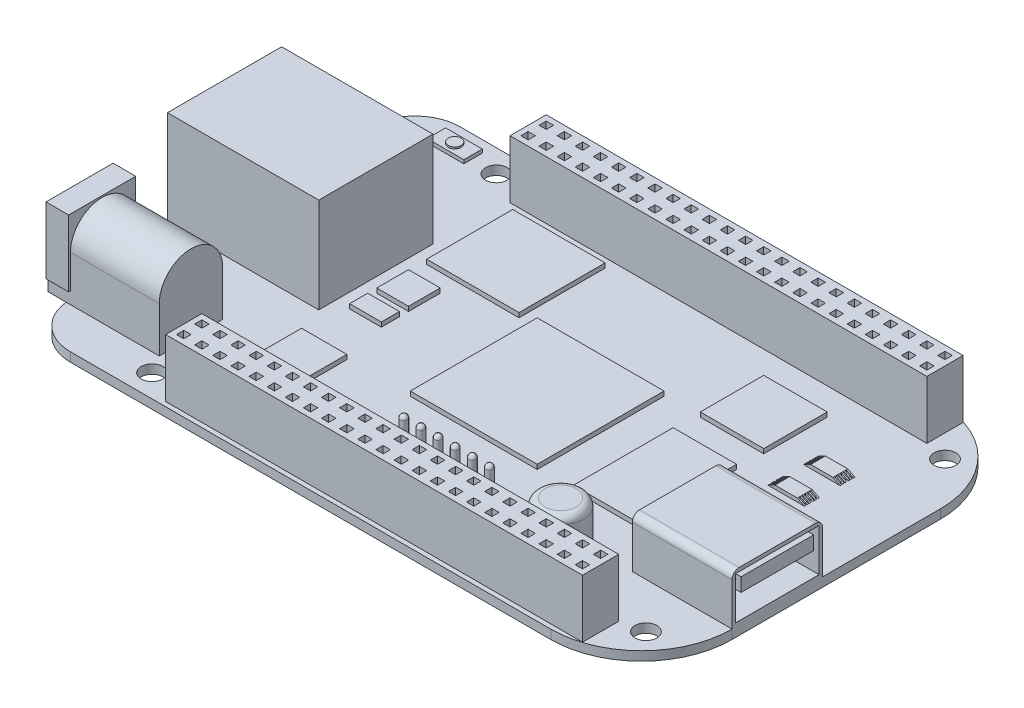
SolidWorks part; units mm, degrees
material "ABS"
ref_plane "Front Plane" through (0, 0, 0) normal (0, 0, 1) x (1, 0, 0)
ref_plane "Top Plane" through (0, 0, 0) normal (0, 1, 0) x (1, 0, 0)
ref_plane "Right Plane" through (0, 0, 0) normal (1, 0, 0) x (0, 0, -1)
sketch "Sketch1" plane through (0, 0, 0) normal (0, 1, 0) x (1, 0, 0)
  line L1 (-12.7, 0) -> (-80.01, 0)
  line L2 (0, 12.7) -> (0, 41.91)
  line L3 (-12.7, 54.61) -> (-80.01, 54.61)
  line L4 (-86.36, 6.35) -> (-86.36, 48.26)
  arc A0 (0, 12.7) -> (-12.7, 0) centre (-12.7, 12.7) cw
  arc A1 (0, 41.91) -> (-12.7, 54.61) centre (-12.7, 41.91) ccw
  arc A2 (-86.36, 6.35) -> (-80.01, 0) centre (-80.01, 6.35) ccw
  arc A3 (-86.36, 48.26) -> (-80.01, 54.61) centre (-80.01, 48.26) cw
  point P7 (0, 0)
  point P10 (0, 54.61)
  point P13 (-86.36, 0)
  dimension "D3" = 12.7
  dimension "D4" = 6.35
  dimension "D1" = 86.36
  dimension "D2" = 54.61
extrude "Boss-Extrude1" add sketch "Sketch1" along normal blind 1.27
sketch "Sketch2" plane through (0, 1.27, 0) normal (0, 1, 0) x (1, 0, 0)
  line L0 (-80.01, 0) -> (-12.7, 0) construction
  line L2 (-71.755, 51.435) -> (-71.755, 3.175) construction
  line L3 (-86.36, 48.26) -> (-86.36, 6.35) construction
  line L4 (-5.715, 48.26) -> (-5.715, 6.35) construction
  circle A0 centre (-71.755, 51.435) radius 1.524
  circle A1 centre (-71.755, 3.175) radius 1.524
  circle A2 centre (-5.715, 48.26) radius 1.524
  circle A3 centre (-5.715, 6.35) radius 1.524
  dimension "D7" = 3.048
  dimension "D1" = 48.26
  dimension "D2" = 41.91
  dimension "D3" = 6.35
  dimension "D4" = 14.605
  dimension "D5" = 80.645
  dimension "D6" = 3.175
extrude "Cut-Extrude1" cut sketch "Sketch2" along direction (0, -1, 0) on the side against the normal up to surface (1.27 mm away) up to face at (-44.4387, 0, -27.305)
sketch "Sketch3" plane through (0, 1.27, 0) normal (0, 1, 0) x (1, 0, 0)
  line L0 (-10.16, 48.895) -> (-10.16, 50.165) construction
  line L1 (-67.31, 53.975) -> (-8.89, 53.975)
  line L2 (-67.31, 53.975) -> (-67.31, 48.895)
  line L3 (-67.31, 48.895) -> (-8.89, 48.895)
  line L4 (-8.89, 53.975) -> (-8.89, 48.895)
  line L5 (-86.36, 27.305) -> (0, 27.305) construction
  line L6 (0, 12.7) -> (0, 41.91) construction
  line L7 (-66.548, 4.953) -> (-66.548, 3.937)
  line L8 (-66.548, 4.953) -> (-65.532, 4.953)
  line L9 (-10.16, 50.165) -> (-10.16, 52.705) construction
  line L10 (-10.16, 52.705) -> (-10.16, 53.975) construction
  line L11 (-13.208, 52.197) -> (-12.192, 52.197)
  line L12 (-10.668, 53.213) -> (-9.652, 53.213)
  line L13 (-10.668, 53.213) -> (-10.668, 52.197)
  line L14 (-10.668, 52.197) -> (-9.652, 52.197)
  line L15 (-9.652, 53.213) -> (-9.652, 52.197)
  line L16 (-10.668, 53.213) -> (-9.652, 52.197) construction
  line L17 (-10.668, 52.197) -> (-9.652, 53.213) construction
  line L18 (-10.668, 49.657) -> (-9.652, 49.657)
  line L19 (-10.668, 49.657) -> (-10.668, 50.673)
  line L20 (-10.668, 50.673) -> (-9.652, 50.673)
  line L21 (-9.652, 49.657) -> (-9.652, 50.673)
  line L22 (-10.668, 49.657) -> (-9.652, 50.673) construction
  line L23 (-10.668, 50.673) -> (-9.652, 49.657) construction
  line L24 (-13.208, 53.213) -> (-13.208, 52.197)
  line L25 (-13.208, 53.213) -> (-12.192, 53.213)
  line L26 (-12.192, 53.213) -> (-12.192, 52.197)
  line L27 (-13.208, 50.673) -> (-12.192, 50.673)
  line L28 (-12.192, 49.657) -> (-12.192, 50.673)
  line L29 (-13.208, 49.657) -> (-12.192, 49.657)
  line L30 (-13.208, 49.657) -> (-13.208, 50.673)
  line L31 (-15.748, 52.197) -> (-14.732, 52.197)
  line L32 (-15.748, 53.213) -> (-15.748, 52.197)
  line L33 (-15.748, 53.213) -> (-14.732, 53.213)
  line L34 (-14.732, 53.213) -> (-14.732, 52.197)
  line L35 (-15.748, 50.673) -> (-14.732, 50.673)
  line L36 (-14.732, 49.657) -> (-14.732, 50.673)
  line L37 (-15.748, 49.657) -> (-14.732, 49.657)
  line L38 (-15.748, 49.657) -> (-15.748, 50.673)
  line L39 (-18.288, 52.197) -> (-17.272, 52.197)
  line L40 (-18.288, 53.213) -> (-18.288, 52.197)
  line L41 (-18.288, 53.213) -> (-17.272, 53.213)
  line L42 (-17.272, 53.213) -> (-17.272, 52.197)
  line L43 (-18.288, 50.673) -> (-17.272, 50.673)
  line L44 (-17.272, 49.657) -> (-17.272, 50.673)
  line L45 (-18.288, 49.657) -> (-17.272, 49.657)
  line L46 (-18.288, 49.657) -> (-18.288, 50.673)
  line L47 (-20.828, 52.197) -> (-19.812, 52.197)
  line L48 (-20.828, 53.213) -> (-20.828, 52.197)
  line L49 (-20.828, 53.213) -> (-19.812, 53.213)
  line L50 (-19.812, 53.213) -> (-19.812, 52.197)
  line L51 (-20.828, 50.673) -> (-19.812, 50.673)
  line L52 (-19.812, 49.657) -> (-19.812, 50.673)
  line L53 (-20.828, 49.657) -> (-19.812, 49.657)
  line L54 (-20.828, 49.657) -> (-20.828, 50.673)
  line L55 (-23.368, 52.197) -> (-22.352, 52.197)
  line L56 (-23.368, 53.213) -> (-23.368, 52.197)
  line L57 (-23.368, 53.213) -> (-22.352, 53.213)
  line L58 (-22.352, 53.213) -> (-22.352, 52.197)
  line L59 (-23.368, 50.673) -> (-22.352, 50.673)
  line L60 (-22.352, 49.657) -> (-22.352, 50.673)
  line L61 (-23.368, 49.657) -> (-22.352, 49.657)
  line L62 (-23.368, 49.657) -> (-23.368, 50.673)
  line L63 (-25.908, 52.197) -> (-24.892, 52.197)
  line L64 (-25.908, 53.213) -> (-25.908, 52.197)
  line L65 (-25.908, 53.213) -> (-24.892, 53.213)
  line L66 (-24.892, 53.213) -> (-24.892, 52.197)
  line L67 (-25.908, 50.673) -> (-24.892, 50.673)
  line L68 (-24.892, 49.657) -> (-24.892, 50.673)
  line L69 (-25.908, 49.657) -> (-24.892, 49.657)
  line L70 (-25.908, 49.657) -> (-25.908, 50.673)
  line L71 (-28.448, 52.197) -> (-27.432, 52.197)
  line L72 (-28.448, 53.213) -> (-28.448, 52.197)
  line L73 (-28.448, 53.213) -> (-27.432, 53.213)
  line L74 (-27.432, 53.213) -> (-27.432, 52.197)
  line L75 (-28.448, 50.673) -> (-27.432, 50.673)
  line L76 (-27.432, 49.657) -> (-27.432, 50.673)
  line L77 (-28.448, 49.657) -> (-27.432, 49.657)
  line L78 (-28.448, 49.657) -> (-28.448, 50.673)
  line L79 (-30.988, 52.197) -> (-29.972, 52.197)
  line L80 (-30.988, 53.213) -> (-30.988, 52.197)
  line L81 (-30.988, 53.213) -> (-29.972, 53.213)
  line L82 (-29.972, 53.213) -> (-29.972, 52.197)
  line L83 (-30.988, 50.673) -> (-29.972, 50.673)
  line L84 (-29.972, 49.657) -> (-29.972, 50.673)
  line L85 (-30.988, 49.657) -> (-29.972, 49.657)
  line L86 (-30.988, 49.657) -> (-30.988, 50.673)
  line L87 (-33.528, 52.197) -> (-32.512, 52.197)
  line L88 (-33.528, 53.213) -> (-33.528, 52.197)
  line L89 (-33.528, 53.213) -> (-32.512, 53.213)
  line L90 (-32.512, 53.213) -> (-32.512, 52.197)
  line L91 (-33.528, 50.673) -> (-32.512, 50.673)
  line L92 (-32.512, 49.657) -> (-32.512, 50.673)
  line L93 (-33.528, 49.657) -> (-32.512, 49.657)
  line L94 (-33.528, 49.657) -> (-33.528, 50.673)
  line L95 (-36.068, 52.197) -> (-35.052, 52.197)
  line L96 (-36.068, 53.213) -> (-36.068, 52.197)
  line L97 (-36.068, 53.213) -> (-35.052, 53.213)
  line L98 (-35.052, 53.213) -> (-35.052, 52.197)
  line L99 (-36.068, 50.673) -> (-35.052, 50.673)
  line L100 (-35.052, 49.657) -> (-35.052, 50.673)
  line L101 (-36.068, 49.657) -> (-35.052, 49.657)
  line L102 (-36.068, 49.657) -> (-36.068, 50.673)
  line L103 (-38.608, 52.197) -> (-37.592, 52.197)
  line L104 (-38.608, 53.213) -> (-38.608, 52.197)
  line L105 (-38.608, 53.213) -> (-37.592, 53.213)
  line L106 (-37.592, 53.213) -> (-37.592, 52.197)
  line L107 (-38.608, 50.673) -> (-37.592, 50.673)
  line L108 (-37.592, 49.657) -> (-37.592, 50.673)
  line L109 (-38.608, 49.657) -> (-37.592, 49.657)
  line L110 (-38.608, 49.657) -> (-38.608, 50.673)
  line L111 (-41.148, 52.197) -> (-40.132, 52.197)
  line L112 (-41.148, 53.213) -> (-41.148, 52.197)
  line L113 (-41.148, 53.213) -> (-40.132, 53.213)
  line L114 (-40.132, 53.213) -> (-40.132, 52.197)
  line L115 (-41.148, 50.673) -> (-40.132, 50.673)
  line L116 (-40.132, 49.657) -> (-40.132, 50.673)
  line L117 (-41.148, 49.657) -> (-40.132, 49.657)
  line L118 (-41.148, 49.657) -> (-41.148, 50.673)
  line L119 (-43.688, 52.197) -> (-42.672, 52.197)
  line L120 (-43.688, 53.213) -> (-43.688, 52.197)
  line L121 (-43.688, 53.213) -> (-42.672, 53.213)
  line L122 (-42.672, 53.213) -> (-42.672, 52.197)
  line L123 (-43.688, 50.673) -> (-42.672, 50.673)
  line L124 (-42.672, 49.657) -> (-42.672, 50.673)
  line L125 (-43.688, 49.657) -> (-42.672, 49.657)
  line L126 (-43.688, 49.657) -> (-43.688, 50.673)
  line L127 (-46.228, 52.197) -> (-45.212, 52.197)
  line L128 (-46.228, 53.213) -> (-46.228, 52.197)
  line L129 (-46.228, 53.213) -> (-45.212, 53.213)
  line L130 (-45.212, 53.213) -> (-45.212, 52.197)
  line L131 (-46.228, 50.673) -> (-45.212, 50.673)
  line L132 (-45.212, 49.657) -> (-45.212, 50.673)
  line L133 (-46.228, 49.657) -> (-45.212, 49.657)
  line L134 (-46.228, 49.657) -> (-46.228, 50.673)
  line L135 (-48.768, 52.197) -> (-47.752, 52.197)
  line L136 (-48.768, 53.213) -> (-48.768, 52.197)
  line L137 (-48.768, 53.213) -> (-47.752, 53.213)
  line L138 (-47.752, 53.213) -> (-47.752, 52.197)
  line L139 (-48.768, 50.673) -> (-47.752, 50.673)
  line L140 (-47.752, 49.657) -> (-47.752, 50.673)
  line L141 (-48.768, 49.657) -> (-47.752, 49.657)
  line L142 (-48.768, 49.657) -> (-48.768, 50.673)
  line L143 (-51.308, 52.197) -> (-50.292, 52.197)
  line L144 (-51.308, 53.213) -> (-51.308, 52.197)
  line L145 (-51.308, 53.213) -> (-50.292, 53.213)
  line L146 (-50.292, 53.213) -> (-50.292, 52.197)
  line L147 (-51.308, 50.673) -> (-50.292, 50.673)
  line L148 (-50.292, 49.657) -> (-50.292, 50.673)
  line L149 (-51.308, 49.657) -> (-50.292, 49.657)
  line L150 (-51.308, 49.657) -> (-51.308, 50.673)
  line L151 (-53.848, 52.197) -> (-52.832, 52.197)
  line L152 (-53.848, 53.213) -> (-53.848, 52.197)
  line L153 (-53.848, 53.213) -> (-52.832, 53.213)
  line L154 (-52.832, 53.213) -> (-52.832, 52.197)
  line L155 (-53.848, 50.673) -> (-52.832, 50.673)
  line L156 (-52.832, 49.657) -> (-52.832, 50.673)
  line L157 (-53.848, 49.657) -> (-52.832, 49.657)
  line L158 (-53.848, 49.657) -> (-53.848, 50.673)
  line L159 (-56.388, 52.197) -> (-55.372, 52.197)
  line L160 (-56.388, 53.213) -> (-56.388, 52.197)
  line L161 (-56.388, 53.213) -> (-55.372, 53.213)
  line L162 (-55.372, 53.213) -> (-55.372, 52.197)
  line L163 (-56.388, 50.673) -> (-55.372, 50.673)
  line L164 (-55.372, 49.657) -> (-55.372, 50.673)
  line L165 (-56.388, 49.657) -> (-55.372, 49.657)
  line L166 (-56.388, 49.657) -> (-56.388, 50.673)
  line L167 (-58.928, 52.197) -> (-57.912, 52.197)
  line L168 (-58.928, 53.213) -> (-58.928, 52.197)
  line L169 (-58.928, 53.213) -> (-57.912, 53.213)
  line L170 (-57.912, 53.213) -> (-57.912, 52.197)
  line L171 (-58.928, 50.673) -> (-57.912, 50.673)
  line L172 (-57.912, 49.657) -> (-57.912, 50.673)
  line L173 (-58.928, 49.657) -> (-57.912, 49.657)
  line L174 (-58.928, 49.657) -> (-58.928, 50.673)
  line L175 (-61.468, 52.197) -> (-60.452, 52.197)
  line L176 (-61.468, 53.213) -> (-61.468, 52.197)
  line L177 (-61.468, 53.213) -> (-60.452, 53.213)
  line L178 (-60.452, 53.213) -> (-60.452, 52.197)
  line L179 (-61.468, 50.673) -> (-60.452, 50.673)
  line L180 (-60.452, 49.657) -> (-60.452, 50.673)
  line L181 (-61.468, 49.657) -> (-60.452, 49.657)
  line L182 (-61.468, 49.657) -> (-61.468, 50.673)
  line L183 (-64.008, 52.197) -> (-62.992, 52.197)
  line L184 (-64.008, 53.213) -> (-64.008, 52.197)
  line L185 (-64.008, 53.213) -> (-62.992, 53.213)
  line L186 (-62.992, 53.213) -> (-62.992, 52.197)
  line L187 (-64.008, 50.673) -> (-62.992, 50.673)
  line L188 (-62.992, 49.657) -> (-62.992, 50.673)
  line L189 (-64.008, 49.657) -> (-62.992, 49.657)
  line L190 (-64.008, 49.657) -> (-64.008, 50.673)
  line L191 (-66.548, 52.197) -> (-65.532, 52.197)
  line L192 (-66.548, 53.213) -> (-66.548, 52.197)
  line L193 (-66.548, 53.213) -> (-65.532, 53.213)
  line L194 (-65.532, 53.213) -> (-65.532, 52.197)
  line L195 (-66.548, 50.673) -> (-65.532, 50.673)
  line L196 (-65.532, 49.657) -> (-65.532, 50.673)
  line L197 (-66.548, 49.657) -> (-65.532, 49.657)
  line L198 (-66.548, 49.657) -> (-66.548, 50.673)
  line L199 (-66.548, 49.657) -> (-65.532, 50.673) construction
  line L200 (-86.36, 48.26) -> (-86.36, 6.35) construction
  line L201 (-65.532, 4.953) -> (-65.532, 3.937)
  line L202 (-12.7, 54.61) -> (-80.01, 54.61) construction
  line L203 (-66.548, 3.937) -> (-65.532, 3.937)
  line L204 (-65.532, 1.397) -> (-65.532, 2.413)
  line L205 (-66.548, 1.397) -> (-65.532, 1.397)
  line L206 (-66.548, 1.397) -> (-66.548, 2.413)
  line L207 (-66.548, 2.413) -> (-65.532, 2.413)
  line L208 (-64.008, 4.953) -> (-64.008, 3.937)
  line L209 (-64.008, 4.953) -> (-62.992, 4.953)
  line L210 (-62.992, 4.953) -> (-62.992, 3.937)
  line L211 (-64.008, 3.937) -> (-62.992, 3.937)
  line L212 (-62.992, 1.397) -> (-62.992, 2.413)
  line L213 (-64.008, 1.397) -> (-62.992, 1.397)
  line L214 (-64.008, 1.397) -> (-64.008, 2.413)
  line L215 (-64.008, 2.413) -> (-62.992, 2.413)
  line L216 (-61.468, 4.953) -> (-61.468, 3.937)
  line L217 (-61.468, 4.953) -> (-60.452, 4.953)
  line L218 (-60.452, 4.953) -> (-60.452, 3.937)
  line L219 (-61.468, 3.937) -> (-60.452, 3.937)
  line L220 (-60.452, 1.397) -> (-60.452, 2.413)
  line L221 (-61.468, 1.397) -> (-60.452, 1.397)
  line L222 (-61.468, 1.397) -> (-61.468, 2.413)
  line L223 (-61.468, 2.413) -> (-60.452, 2.413)
  line L224 (-58.928, 4.953) -> (-58.928, 3.937)
  line L225 (-58.928, 4.953) -> (-57.912, 4.953)
  line L226 (-57.912, 4.953) -> (-57.912, 3.937)
  line L227 (-58.928, 3.937) -> (-57.912, 3.937)
  line L228 (-57.912, 1.397) -> (-57.912, 2.413)
  line L229 (-58.928, 1.397) -> (-57.912, 1.397)
  line L230 (-58.928, 1.397) -> (-58.928, 2.413)
  line L231 (-58.928, 2.413) -> (-57.912, 2.413)
  line L232 (-56.388, 4.953) -> (-56.388, 3.937)
  line L233 (-56.388, 4.953) -> (-55.372, 4.953)
  line L234 (-55.372, 4.953) -> (-55.372, 3.937)
  line L235 (-56.388, 3.937) -> (-55.372, 3.937)
  line L236 (-55.372, 1.397) -> (-55.372, 2.413)
  line L237 (-56.388, 1.397) -> (-55.372, 1.397)
  line L238 (-56.388, 1.397) -> (-56.388, 2.413)
  line L239 (-56.388, 2.413) -> (-55.372, 2.413)
  line L240 (-53.848, 4.953) -> (-53.848, 3.937)
  line L241 (-53.848, 4.953) -> (-52.832, 4.953)
  line L242 (-52.832, 4.953) -> (-52.832, 3.937)
  line L243 (-53.848, 3.937) -> (-52.832, 3.937)
  line L244 (-52.832, 1.397) -> (-52.832, 2.413)
  line L245 (-53.848, 1.397) -> (-52.832, 1.397)
  line L246 (-53.848, 1.397) -> (-53.848, 2.413)
  line L247 (-53.848, 2.413) -> (-52.832, 2.413)
  line L248 (-51.308, 4.953) -> (-51.308, 3.937)
  line L249 (-51.308, 4.953) -> (-50.292, 4.953)
  line L250 (-50.292, 4.953) -> (-50.292, 3.937)
  line L251 (-51.308, 3.937) -> (-50.292, 3.937)
  line L252 (-50.292, 1.397) -> (-50.292, 2.413)
  line L253 (-51.308, 1.397) -> (-50.292, 1.397)
  line L254 (-51.308, 1.397) -> (-51.308, 2.413)
  line L255 (-51.308, 2.413) -> (-50.292, 2.413)
  line L256 (-48.768, 4.953) -> (-48.768, 3.937)
  line L257 (-48.768, 4.953) -> (-47.752, 4.953)
  line L258 (-47.752, 4.953) -> (-47.752, 3.937)
  line L259 (-48.768, 3.937) -> (-47.752, 3.937)
  line L260 (-47.752, 1.397) -> (-47.752, 2.413)
  line L261 (-48.768, 1.397) -> (-47.752, 1.397)
  line L262 (-48.768, 1.397) -> (-48.768, 2.413)
  line L263 (-48.768, 2.413) -> (-47.752, 2.413)
  line L264 (-46.228, 4.953) -> (-46.228, 3.937)
  line L265 (-46.228, 4.953) -> (-45.212, 4.953)
  line L266 (-45.212, 4.953) -> (-45.212, 3.937)
  line L267 (-46.228, 3.937) -> (-45.212, 3.937)
  line L268 (-45.212, 1.397) -> (-45.212, 2.413)
  line L269 (-46.228, 1.397) -> (-45.212, 1.397)
  line L270 (-46.228, 1.397) -> (-46.228, 2.413)
  line L271 (-46.228, 2.413) -> (-45.212, 2.413)
  line L272 (-43.688, 4.953) -> (-43.688, 3.937)
  line L273 (-43.688, 4.953) -> (-42.672, 4.953)
  line L274 (-42.672, 4.953) -> (-42.672, 3.937)
  line L275 (-43.688, 3.937) -> (-42.672, 3.937)
  line L276 (-42.672, 1.397) -> (-42.672, 2.413)
  line L277 (-43.688, 1.397) -> (-42.672, 1.397)
  line L278 (-43.688, 1.397) -> (-43.688, 2.413)
  line L279 (-43.688, 2.413) -> (-42.672, 2.413)
  line L280 (-41.148, 4.953) -> (-41.148, 3.937)
  line L281 (-41.148, 4.953) -> (-40.132, 4.953)
  line L282 (-40.132, 4.953) -> (-40.132, 3.937)
  line L283 (-41.148, 3.937) -> (-40.132, 3.937)
  line L284 (-40.132, 1.397) -> (-40.132, 2.413)
  line L285 (-41.148, 1.397) -> (-40.132, 1.397)
  line L286 (-41.148, 1.397) -> (-41.148, 2.413)
  line L287 (-41.148, 2.413) -> (-40.132, 2.413)
  line L288 (-38.608, 4.953) -> (-38.608, 3.937)
  line L289 (-38.608, 4.953) -> (-37.592, 4.953)
  line L290 (-37.592, 4.953) -> (-37.592, 3.937)
  line L291 (-38.608, 3.937) -> (-37.592, 3.937)
  line L292 (-37.592, 1.397) -> (-37.592, 2.413)
  line L293 (-38.608, 1.397) -> (-37.592, 1.397)
  line L294 (-38.608, 1.397) -> (-38.608, 2.413)
  line L295 (-38.608, 2.413) -> (-37.592, 2.413)
  line L296 (-36.068, 4.953) -> (-36.068, 3.937)
  line L297 (-36.068, 4.953) -> (-35.052, 4.953)
  line L298 (-35.052, 4.953) -> (-35.052, 3.937)
  line L299 (-36.068, 3.937) -> (-35.052, 3.937)
  line L300 (-35.052, 1.397) -> (-35.052, 2.413)
  line L301 (-36.068, 1.397) -> (-35.052, 1.397)
  line L302 (-36.068, 1.397) -> (-36.068, 2.413)
  line L303 (-36.068, 2.413) -> (-35.052, 2.413)
  line L304 (-33.528, 4.953) -> (-33.528, 3.937)
  line L305 (-33.528, 4.953) -> (-32.512, 4.953)
  line L306 (-32.512, 4.953) -> (-32.512, 3.937)
  line L307 (-33.528, 3.937) -> (-32.512, 3.937)
  line L308 (-32.512, 1.397) -> (-32.512, 2.413)
  line L309 (-33.528, 1.397) -> (-32.512, 1.397)
  line L310 (-33.528, 1.397) -> (-33.528, 2.413)
  line L311 (-33.528, 2.413) -> (-32.512, 2.413)
  line L312 (-30.988, 4.953) -> (-30.988, 3.937)
  line L313 (-30.988, 4.953) -> (-29.972, 4.953)
  line L314 (-29.972, 4.953) -> (-29.972, 3.937)
  line L315 (-30.988, 3.937) -> (-29.972, 3.937)
  line L316 (-29.972, 1.397) -> (-29.972, 2.413)
  line L317 (-30.988, 1.397) -> (-29.972, 1.397)
  line L318 (-30.988, 1.397) -> (-30.988, 2.413)
  line L319 (-30.988, 2.413) -> (-29.972, 2.413)
  line L320 (-28.448, 4.953) -> (-28.448, 3.937)
  line L321 (-28.448, 4.953) -> (-27.432, 4.953)
  line L322 (-27.432, 4.953) -> (-27.432, 3.937)
  line L323 (-28.448, 3.937) -> (-27.432, 3.937)
  line L324 (-27.432, 1.397) -> (-27.432, 2.413)
  line L325 (-28.448, 1.397) -> (-27.432, 1.397)
  line L326 (-28.448, 1.397) -> (-28.448, 2.413)
  line L327 (-28.448, 2.413) -> (-27.432, 2.413)
  line L328 (-25.908, 4.953) -> (-25.908, 3.937)
  line L329 (-25.908, 4.953) -> (-24.892, 4.953)
  line L330 (-24.892, 4.953) -> (-24.892, 3.937)
  line L331 (-25.908, 3.937) -> (-24.892, 3.937)
  line L332 (-24.892, 1.397) -> (-24.892, 2.413)
  line L333 (-25.908, 1.397) -> (-24.892, 1.397)
  line L334 (-25.908, 1.397) -> (-25.908, 2.413)
  line L335 (-25.908, 2.413) -> (-24.892, 2.413)
  line L336 (-23.368, 4.953) -> (-23.368, 3.937)
  line L337 (-23.368, 4.953) -> (-22.352, 4.953)
  line L338 (-22.352, 4.953) -> (-22.352, 3.937)
  line L339 (-23.368, 3.937) -> (-22.352, 3.937)
  line L340 (-22.352, 1.397) -> (-22.352, 2.413)
  line L341 (-23.368, 1.397) -> (-22.352, 1.397)
  line L342 (-23.368, 1.397) -> (-23.368, 2.413)
  line L343 (-23.368, 2.413) -> (-22.352, 2.413)
  line L344 (-20.828, 4.953) -> (-20.828, 3.937)
  line L345 (-20.828, 4.953) -> (-19.812, 4.953)
  line L346 (-19.812, 4.953) -> (-19.812, 3.937)
  line L347 (-20.828, 3.937) -> (-19.812, 3.937)
  line L348 (-19.812, 1.397) -> (-19.812, 2.413)
  line L349 (-20.828, 1.397) -> (-19.812, 1.397)
  line L350 (-20.828, 1.397) -> (-20.828, 2.413)
  line L351 (-20.828, 2.413) -> (-19.812, 2.413)
  line L352 (-18.288, 4.953) -> (-18.288, 3.937)
  line L353 (-18.288, 4.953) -> (-17.272, 4.953)
  line L354 (-17.272, 4.953) -> (-17.272, 3.937)
  line L355 (-18.288, 3.937) -> (-17.272, 3.937)
  line L356 (-17.272, 1.397) -> (-17.272, 2.413)
  line L357 (-18.288, 1.397) -> (-17.272, 1.397)
  line L358 (-18.288, 1.397) -> (-18.288, 2.413)
  line L359 (-18.288, 2.413) -> (-17.272, 2.413)
  line L360 (-15.748, 4.953) -> (-15.748, 3.937)
  line L361 (-15.748, 4.953) -> (-14.732, 4.953)
  line L362 (-14.732, 4.953) -> (-14.732, 3.937)
  line L363 (-15.748, 3.937) -> (-14.732, 3.937)
  line L364 (-14.732, 1.397) -> (-14.732, 2.413)
  line L365 (-15.748, 1.397) -> (-14.732, 1.397)
  line L366 (-15.748, 1.397) -> (-15.748, 2.413)
  line L367 (-15.748, 2.413) -> (-14.732, 2.413)
  line L368 (-13.208, 4.953) -> (-13.208, 3.937)
  line L369 (-13.208, 4.953) -> (-12.192, 4.953)
  line L370 (-12.192, 4.953) -> (-12.192, 3.937)
  line L371 (-13.208, 3.937) -> (-12.192, 3.937)
  line L372 (-12.192, 1.397) -> (-12.192, 2.413)
  line L373 (-13.208, 1.397) -> (-12.192, 1.397)
  line L374 (-13.208, 1.397) -> (-13.208, 2.413)
  line L375 (-9.652, 4.953) -> (-9.652, 3.937)
  line L376 (-10.668, 3.937) -> (-9.652, 3.937)
  line L377 (-10.668, 4.953) -> (-10.668, 3.937)
  line L378 (-10.668, 4.953) -> (-9.652, 4.953)
  line L379 (-9.652, 1.397) -> (-9.652, 2.413)
  line L380 (-10.668, 2.413) -> (-9.652, 2.413)
  line L381 (-10.668, 1.397) -> (-10.668, 2.413)
  line L382 (-10.668, 1.397) -> (-9.652, 1.397)
  line L383 (-13.208, 2.413) -> (-12.192, 2.413)
  line L384 (-8.89, 0.635) -> (-8.89, 5.715)
  line L385 (-67.31, 5.715) -> (-8.89, 5.715)
  line L386 (-67.31, 0.635) -> (-67.31, 5.715)
  line L387 (-67.31, 0.635) -> (-8.89, 0.635)
  circle A0 centre (-66.04, 50.165) radius 0.1361
  dimension "D1" = 1.016
  dimension "D2" = 2.54
  dimension "D3" = 5.08
  dimension "D4" = 58.42
  dimension "D5" = 1.27
  dimension "D7" = 20.32
  dimension "D8" = 0.635
  dimension "D6" = 23
extrude "Boss-Extrude2" add sketch "Sketch3" along normal blind 8.128 contours L4 L1 L2 L3 L193 L194 L191 L192 L185 L186 L183 L184 L177 L178 L175 L176 L169 L170 L167 L168 L161 L162 L159 L160 L153 L154 L151 L152 L145 L146 L143 L144 L137 L138 L135 L136 L129 L130 L127 L128 L121 | L386 L387 L384 L385 L374 L383 L372 L373 L382 L381 L380 L379 L366 L367 L364 L365 L363 L360 L361 L362 L350 L351 L348 L349 L347 L344 L345 L346 L334 L335 L332 L333 L331 L328 L329 L330 L318 L319 L316 L317 L315 region at (-38.1, 1.27, -51.435) region at (-38.1, 1.27, -3.175)
sketch "Sketch4" plane through (0, 1.27, 0) normal (0, 1, 0) x (1, 0, 0)
  line L0 (-86.36, 48.26) -> (-86.36, 6.35) construction
  line L1 (-67.691, 22.479) -> (-88.9, 22.479)
  line L2 (-67.691, 22.479) -> (-67.691, 38.481)
  line L3 (-67.691, 38.481) -> (-88.9, 38.481)
  line L4 (-88.9, 22.479) -> (-88.9, 38.481)
  line L5 (-12.7, 54.61) -> (-80.01, 54.61) construction
  dimension "D1" = 2.54
  dimension "D2" = 21.209
  dimension "D3" = 16.002
  dimension "D4" = 16.129
extrude "Boss-Extrude3" add sketch "Sketch4" along normal blind 13.335
sketch "Sketch5" plane through (-88.9, 0, 0) normal (-1, 0, 0) x (0, 0, 1)
  line L0 (-30.48, 2.286) -> (-30.48, 3.937) construction
  line L1 (-36.83, 12.065) -> (-24.13, 12.065)
  line L2 (-36.83, 12.065) -> (-36.83, 5.461)
  line L3 (-36.83, 5.461) -> (-24.13, 5.461)
  line L4 (-24.13, 12.065) -> (-24.13, 5.461)
  line L5 (-33.655, 5.461) -> (-27.305, 5.461)
  line L6 (-33.655, 5.461) -> (-33.655, 3.937)
  line L7 (-33.655, 3.937) -> (-27.305, 3.937)
  line L8 (-27.305, 5.461) -> (-27.305, 3.937)
  line L9 (-32.512, 3.937) -> (-28.448, 3.937)
  line L10 (-32.512, 3.937) -> (-32.512, 2.286)
  line L11 (-32.512, 2.286) -> (-28.448, 2.286)
  line L12 (-28.448, 3.937) -> (-28.448, 2.286)
  line L13 (-30.48, 3.937) -> (-30.48, 5.461) construction
  line L14 (-38.481, 14.605) -> (-22.479, 14.605) construction
  line L15 (-36.83, 12.065) -> (-38.481, 12.065) construction
  line L16 (-38.481, 14.605) -> (-38.481, 1.27) construction
  line L17 (-24.13, 12.065) -> (-22.479, 12.065) construction
  line L18 (-22.479, 14.605) -> (-22.479, 1.27) construction
  dimension "D1" = 12.7
  dimension "D2" = 6.604
  dimension "D3" = 2.54
  dimension "D4" = 1.524
  dimension "D5" = 1.651
  dimension "D6" = 4.064
  dimension "D7" = 6.35
extrude "Cut-Extrude2" cut sketch "Sketch5" against normal blind 17.78 contours L4 L1 L2 L3 | L8 L3 L6 L7 | L12 L7 L10 L11 region at (-88.9, 8.763, -30.48) region at (-88.9, 4.699, -30.48) region at (-88.9, 3.1115, -30.48)
sketch "Sketch6" plane through (0, 1.27, 0) normal (0, 1, 0) x (1, 0, 0)
  line L0 (-67.31, 48.895) -> (-8.89, 48.895) construction
  line L1 (-65.659, 35.56) -> (-52.705, 35.56)
  line L2 (-65.659, 35.56) -> (-65.659, 47.625)
  line L3 (-65.659, 47.625) -> (-52.705, 47.625)
  line L4 (-52.705, 35.56) -> (-52.705, 47.625)
  line L5 (-50.8, 36.195) -> (-33.02, 36.195)
  line L6 (-50.8, 36.195) -> (-50.8, 18.415)
  line L7 (-50.8, 18.415) -> (-33.02, 18.415)
  line L8 (-33.02, 36.195) -> (-33.02, 18.415)
  line L9 (-27.94, 45.085) -> (-19.05, 45.085)
  line L10 (-27.94, 45.085) -> (-27.94, 36.195)
  line L11 (-27.94, 36.195) -> (-19.05, 36.195)
  line L12 (-19.05, 45.085) -> (-19.05, 36.195)
  line L13 (-27.94, 32.385) -> (-19.05, 32.385)
  line L14 (-27.94, 32.385) -> (-27.94, 18.415)
  line L15 (-27.94, 18.415) -> (-19.05, 18.415)
  line L16 (-19.05, 32.385) -> (-19.05, 18.415)
  line L17 (-66.04, 18.415) -> (-59.69, 18.415)
  line L18 (-66.04, 18.415) -> (-66.04, 12.065)
  line L19 (-66.04, 12.065) -> (-59.69, 12.065)
  line L20 (-59.69, 18.415) -> (-59.69, 12.065)
  line L21 (-65.659, 27.305) -> (-61.214, 27.305)
  line L22 (-65.659, 27.305) -> (-65.659, 24.765)
  line L23 (-65.659, 24.765) -> (-61.214, 24.765)
  line L24 (-61.214, 27.305) -> (-61.214, 24.765)
  line L25 (-65.659, 33.02) -> (-61.214, 33.02)
  line L26 (-65.659, 33.02) -> (-65.659, 28.575)
  line L27 (-65.659, 28.575) -> (-61.214, 28.575)
  line L28 (-61.214, 33.02) -> (-61.214, 28.575)
  line L29 (0, 12.7) -> (0, 41.91) construction
  line L30 (-67.31, 48.895) -> (-8.89, 48.895) construction
  line L31 (-67.31, 5.715) -> (-8.89, 5.715) construction
  line L33 (-67.31, 0.635) -> (-67.31, 5.715) construction
  dimension "D1" = 8.89
  dimension "D2" = 13.97
  dimension "D3" = 3.81
  dimension "D4" = 3.81
  dimension "D5" = 19.05
  dimension "D6" = 17.78
  dimension "D7" = 12.7
  dimension "D8" = 33.02
  dimension "D9" = 12.954
  dimension "D10" = 12.065
  dimension "D11" = 1.905
  dimension "D12" = 4.445
  dimension "D13" = 2.54
  dimension "D14" = 1.27
  dimension "D15" = 2.54
  dimension "D16" = 1.27
  dimension "D17" = 6.35
  dimension "D18" = 6.35
  dimension "D19" = 1.27
extrude "Boss-Extrude4" add sketch "Sketch6" along normal blind 0.635
sketch "Sketch7" plane through (0, 1.27, 0) normal (0, 1, 0) x (1, 0, 0)
  line L1 (0, 12.7) -> (-13.97, 12.7)
  line L2 (0, 12.7) -> (0, 25.4)
  line L3 (0, 25.4) -> (-13.97, 25.4)
  line L4 (-13.97, 12.7) -> (-13.97, 25.4)
  line L5 (-80.01, 0) -> (-12.7, 0) construction
  line L6 (0, 12.7) -> (0, 41.91) construction
  dimension "D1" = 12.7
  dimension "D2" = 13.97
  dimension "D3" = 25.4
extrude "Boss-Extrude5" add sketch "Sketch7" along normal blind 6.985
sketch "Sketch8" plane through (0, 0, 0) normal (1, 0, 0) x (0, 0, -1)
  line L0 (12.7, 8.255) -> (25.4, 8.255) construction
  line L1 (13.97, 6.985) -> (24.13, 6.985)
  line L2 (13.97, 6.985) -> (13.97, 5.08)
  line L3 (13.97, 5.08) -> (24.13, 5.08)
  line L4 (24.13, 6.985) -> (24.13, 5.08)
  line L5 (13.208, 7.747) -> (24.892, 7.747)
  line L6 (13.208, 7.747) -> (13.208, 1.778)
  line L7 (13.208, 1.778) -> (24.892, 1.778)
  line L8 (24.892, 7.747) -> (24.892, 1.778)
  line L9 (25.4, 8.255) -> (25.4, 1.27) construction
  line L10 (12.7, 8.255) -> (12.7, 1.27) construction
  line L11 (12.7, 1.27) -> (0, 1.27) construction
  line L12 (13.97, 7.18) -> (13.208, 7.18) construction
  line L14 (24.892, 6.9479) -> (24.13, 6.9479) construction
  dimension "D1" = 0.508
  dimension "D2" = 0.508
  dimension "D3" = 0.508
  dimension "D4" = 0.508
  dimension "D5" = 1.905
  dimension "D6" = 10.16
  dimension "D7" = 3.175
extrude "Cut-Extrude3" cut sketch "Sketch8" against normal blind 12.7
sketch "Sketch9" plane through (0, 1.27, 0) normal (0, 1, 0) x (1, 0, 0)
  line L0 (-88.9, 38.481) -> (-88.9, 22.479) construction
  line L1 (-73.279, 5.715) -> (-88.9, 5.715)
  line L2 (-73.279, 5.715) -> (-73.279, 14.605)
  line L3 (-73.279, 14.605) -> (-88.9, 14.605)
  line L4 (-88.9, 5.715) -> (-88.9, 14.605)
  line L5 (-67.31, 5.715) -> (-8.89, 5.715) construction
  circle A0 centre (-71.755, 3.175) radius 1.524 construction
  dimension "D1" = 8.89
extrude "Boss-Extrude6" add sketch "Sketch9" along normal blind 6.35
sketch "Sketch10" plane through (-88.9, 0, 0) normal (-1, 0, 0) x (0, 0, 1)
  line L0 (-14.605, 7.62) -> (-5.715, 7.62) construction
  circle A0 centre (-10.16, 7.62) radius 4.445
  circle A1 centre (-10.16, 7.62) radius 3.4925
  circle A2 centre (-10.16, 7.62) radius 0.635
  line M3 (-5.715, 7.62) -> (-14.605, 7.62)
  dimension "D1" = 1.27
  dimension "D2" = 6.985
extrude "Boss-Extrude7" add sketch "Sketch10" along direction (1, 0, 0) on the side against the normal up to surface (15.621 mm away) contours A1 A0 M3 | A1 A0 M3 | A2 M3 | A2 A1 M3 region at (-88.9, 7.7194, -6.1912) region at (-88.9, 3.2744, -10.16) region at (-88.9, 9.1437, -10.16) region at (-88.9, 7.8895, -10.16) up to face at (-73.279, 4.445, -10.16)
sketch "Sketch11" plane through (-88.9, 0, 0) normal (-1, 0, 0) x (0, 0, 1)
  line L0 (-14.605, 7.62) -> (-14.605, 1.27) construction
  line L1 (-5.461, 2.952) -> (-14.859, 2.952)
  line L2 (-5.461, 2.952) -> (-5.461, 12.288)
  line L3 (-5.461, 12.288) -> (-14.859, 12.288)
  line L4 (-14.859, 2.952) -> (-14.859, 12.288)
  line L5 (-5.461, 2.952) -> (-14.859, 12.288) construction
  line L6 (-5.461, 12.288) -> (-14.859, 2.952) construction
  point P0 (-10.16, 7.62)
  dimension "D1" = 0.254
extrude "Boss-Extrude8" add sketch "Sketch11" against normal blind 3.175
extrude "Cut-Extrude4" cut sketch "Sketch10<3>" against normal blind 12.7 contours A2 A1 M3 | A2 A1 M3 region at (-88.9, 9.1437, -10.16) region at (-88.9, 6.0963, -10.16)
sketch "Sketch10<3>" plane through (-88.9, 0, 0) normal (-1, 0, 0) x (0, 0, 1) same geometry as "Sketch10"
fillet "Fillet1" radius 0.635 1 edges at (-88.9, 7.62, -9.525)
sketch "Sketch13" plane through (0, 1.27, 0) normal (0, 1, 0) x (1, 0, 0)
  line L0 (-85.1081, 45.625) -> (-85.1081, 44.3766)
  line L1 (-80.4022, 50.3766) -> (-80.4022, 52.967)
  line L2 (-80.4022, 40.3766) -> (-75.2569, 40.3766)
  line L3 (-80.4022, 40.3766) -> (-80.4022, 42.967)
  line L4 (-80.4022, 42.967) -> (-75.2569, 42.967)
  line L5 (-85.1081, 47.625) -> (-81.6152, 47.625)
  line L6 (-85.1081, 47.625) -> (-85.1081, 46.3766)
  line L7 (-85.1081, 46.3766) -> (-81.6152, 46.3766)
  line L8 (-81.6152, 47.625) -> (-81.6152, 46.3766)
  line L9 (-85.1081, 45.625) -> (-81.6152, 45.625)
  line L10 (-81.6152, 45.625) -> (-81.6152, 44.3766)
  line L11 (-85.1081, 44.3766) -> (-81.6152, 44.3766)
  line L12 (-85.1081, 43.625) -> (-85.1081, 42.3766)
  line L13 (-85.1081, 43.625) -> (-81.6152, 43.625)
  line L14 (-81.6152, 43.625) -> (-81.6152, 42.3766)
  line L15 (-85.1081, 42.3766) -> (-81.6152, 42.3766)
  line L16 (-85.1081, 41.625) -> (-85.1081, 40.3766)
  line L17 (-85.1081, 41.625) -> (-81.6152, 41.625)
  line L18 (-81.6152, 41.625) -> (-81.6152, 40.3766)
  line L19 (-85.1081, 40.3766) -> (-81.6152, 40.3766)
  line L20 (-75.2569, 40.3766) -> (-75.2569, 42.967)
  line L21 (-80.4022, 50.3766) -> (-75.2569, 50.3766)
  line L22 (-75.2569, 50.3766) -> (-75.2569, 52.967)
  line L23 (-80.4022, 52.967) -> (-75.2569, 52.967)
  line L24 (-9.8278, 38.5983) -> (-9.8278, 38.3983)
  line L25 (-9.8278, 34.5526) -> (-9.8278, 34.7526)
  line L26 (-10.8276, 33.5983) -> (-9.8278, 33.5983)
  line L27 (-10.8276, 33.5983) -> (-10.8276, 33.3983)
  line L28 (-10.8276, 33.3983) -> (-9.8278, 33.3983)
  line L29 (-13.97, 34.7526) -> (-10.8276, 34.7526)
  line L30 (-13.97, 34.7526) -> (-13.97, 32.6861)
  line L31 (-13.97, 32.6861) -> (-10.8276, 32.6861)
  line L32 (-10.8276, 34.7526) -> (-10.8276, 32.6861)
  line L33 (-10.8276, 39.1779) -> (-9.8278, 39.1779)
  line L34 (-10.8276, 38.8404) -> (-9.8278, 38.8404)
  line L35 (-13.97, 38.3983) -> (-14.9698, 38.3983)
  line L36 (-10.8276, 39.7526) -> (-10.8276, 37.6861)
  line L37 (-9.8278, 33.5983) -> (-9.8278, 33.3983)
  line L38 (-10.8276, 33.2607) -> (-9.8278, 33.2607)
  line L39 (-10.8276, 33.2607) -> (-10.8276, 33.0607)
  line L40 (-10.8276, 33.0607) -> (-9.8278, 33.0607)
  line L41 (-9.8278, 33.2607) -> (-9.8278, 33.0607)
  line L42 (-10.8276, 32.8861) -> (-9.8278, 32.8861)
  line L43 (-10.8276, 32.8861) -> (-10.8276, 32.6861)
  line L44 (-10.8276, 32.6861) -> (-9.8278, 32.6861)
  line L45 (-9.8278, 32.8861) -> (-9.8278, 32.6861)
  line L46 (-10.8276, 34.7526) -> (-9.8278, 34.7526)
  line L47 (-10.8276, 34.5526) -> (-10.8276, 34.7526)
  line L48 (-10.8276, 34.5526) -> (-9.8278, 34.5526)
  line L49 (-9.8278, 34.1779) -> (-9.8278, 34.3779)
  line L50 (-10.8276, 34.3779) -> (-9.8278, 34.3779)
  line L51 (-10.8276, 34.1779) -> (-10.8276, 34.3779)
  line L52 (-10.8276, 34.1779) -> (-9.8278, 34.1779)
  line L53 (-9.8278, 33.8404) -> (-9.8278, 34.0404)
  line L54 (-10.8276, 34.0404) -> (-9.8278, 34.0404)
  line L55 (-10.8276, 33.8404) -> (-10.8276, 34.0404)
  line L56 (-10.8276, 33.8404) -> (-9.8278, 33.8404)
  line L57 (-10.8276, 39.5526) -> (-9.8278, 39.5526)
  line L58 (-13.97, 33.8404) -> (-14.9698, 33.8404)
  line L59 (-13.97, 33.8404) -> (-13.97, 34.0404)
  line L60 (-13.97, 34.0404) -> (-14.9698, 34.0404)
  line L61 (-14.9698, 33.8404) -> (-14.9698, 34.0404)
  line L62 (-13.97, 34.1779) -> (-14.9698, 34.1779)
  line L63 (-13.97, 34.1779) -> (-13.97, 34.3779)
  line L64 (-13.97, 34.3779) -> (-14.9698, 34.3779)
  line L65 (-14.9698, 34.1779) -> (-14.9698, 34.3779)
  line L66 (-13.97, 34.5526) -> (-14.9698, 34.5526)
  line L67 (-13.97, 34.5526) -> (-13.97, 34.7526)
  line L68 (-13.97, 34.7526) -> (-14.9698, 34.7526)
  line L69 (-14.9698, 32.8861) -> (-14.9698, 32.6861)
  line L70 (-13.97, 32.6861) -> (-14.9698, 32.6861)
  line L71 (-13.97, 32.8861) -> (-13.97, 32.6861)
  line L72 (-13.97, 32.8861) -> (-14.9698, 32.8861)
  line L73 (-14.9698, 33.2607) -> (-14.9698, 33.0607)
  line L74 (-13.97, 33.0607) -> (-14.9698, 33.0607)
  line L75 (-13.97, 33.2607) -> (-13.97, 33.0607)
  line L76 (-13.97, 33.2607) -> (-14.9698, 33.2607)
  line L77 (-14.9698, 33.5983) -> (-14.9698, 33.3983)
  line L78 (-13.97, 34.7526) -> (-13.97, 32.6861)
  line L79 (-13.97, 33.3983) -> (-14.9698, 33.3983)
  line L80 (-13.97, 33.5983) -> (-13.97, 33.3983)
  line L81 (-13.97, 33.5983) -> (-14.9698, 33.5983)
  line L82 (-14.9698, 34.5526) -> (-14.9698, 34.7526)
  line L83 (-13.97, 39.3779) -> (-14.9698, 39.3779)
  line L84 (-14.9698, 37.8861) -> (-14.9698, 37.6861)
  line L85 (-10.8276, 37.8861) -> (-9.8278, 37.8861)
  line L86 (-10.8276, 39.1779) -> (-10.8276, 39.3779)
  line L87 (-13.97, 38.2607) -> (-14.9698, 38.2607)
  line L88 (-14.9698, 38.8404) -> (-14.9698, 39.0404)
  line L89 (-14.9698, 39.5526) -> (-14.9698, 39.7526)
  line L90 (-9.8278, 37.8861) -> (-9.8278, 37.6861)
  line L91 (-13.97, 39.7526) -> (-14.9698, 39.7526)
  line L92 (-14.9698, 38.2607) -> (-14.9698, 38.0607)
  line L93 (-10.8276, 38.3983) -> (-9.8278, 38.3983)
  line L94 (-13.97, 38.8404) -> (-14.9698, 38.8404)
  line L95 (-13.97, 38.5983) -> (-13.97, 38.3983)
  line L96 (-10.8276, 38.5983) -> (-10.8276, 38.3983)
  line L97 (-14.9698, 39.1779) -> (-14.9698, 39.3779)
  line L98 (-13.97, 37.6861) -> (-14.9698, 37.6861)
  line L99 (-13.97, 39.7526) -> (-10.8276, 39.7526)
  line L100 (-10.8276, 38.2607) -> (-10.8276, 38.0607)
  line L101 (-9.8278, 38.2607) -> (-9.8278, 38.0607)
  line L102 (-14.9698, 38.5983) -> (-14.9698, 38.3983)
  line L103 (-9.8278, 39.5526) -> (-9.8278, 39.7526)
  line L104 (-13.97, 39.1779) -> (-14.9698, 39.1779)
  line L105 (-13.97, 37.6861) -> (-10.8276, 37.6861)
  line L106 (-10.8276, 39.7526) -> (-9.8278, 39.7526)
  line L107 (-13.97, 38.0607) -> (-14.9698, 38.0607)
  line L108 (-9.8278, 38.8404) -> (-9.8278, 39.0404)
  line L109 (-13.97, 38.8404) -> (-13.97, 39.0404)
  line L110 (-13.97, 38.5983) -> (-14.9698, 38.5983)
  line L111 (-13.97, 39.7526) -> (-13.97, 37.6861)
  line L112 (-10.8276, 39.5526) -> (-10.8276, 39.7526)
  line L113 (-13.97, 39.5526) -> (-14.9698, 39.5526)
  line L114 (-13.97, 37.8861) -> (-13.97, 37.6861)
  line L115 (-10.8276, 38.2607) -> (-9.8278, 38.2607)
  line L116 (-10.8276, 38.0607) -> (-9.8278, 38.0607)
  line L117 (-10.8276, 39.3779) -> (-9.8278, 39.3779)
  line L118 (-10.8276, 38.8404) -> (-10.8276, 39.0404)
  line L119 (-13.97, 39.7526) -> (-13.97, 37.6861)
  line L120 (-10.8276, 38.5983) -> (-9.8278, 38.5983)
  line L121 (-13.97, 39.1779) -> (-13.97, 39.3779)
  line L122 (-10.8276, 37.8861) -> (-10.8276, 37.6861)
  line L123 (-9.8278, 39.1779) -> (-9.8278, 39.3779)
  line L124 (-10.8276, 39.0404) -> (-9.8278, 39.0404)
  line L125 (-13.97, 38.2607) -> (-13.97, 38.0607)
  line L126 (-13.97, 39.0404) -> (-14.9698, 39.0404)
  line L127 (-10.8276, 37.6861) -> (-9.8278, 37.6861)
  line L128 (-13.97, 39.5526) -> (-13.97, 39.7526)
  line L129 (-13.97, 37.8861) -> (-14.9698, 37.8861)
  dimension "D1" = 4
  dimension "D2" = 2
extrude "Boss-Extrude9" add sketch "Sketch13" along normal blind 0.5 contours L23 L1 L21 L22 | L16 L19 L18 L17 | L12 L15 L14 L13 | L0 L11 L10 L9 | L8 L5 L6 L7 | L2 L20 L4 L3 | L99 L111 L109 L95 L105 L36 | L113 L111 L91 L89 | L95 L110 L102 L35 | L111 L129 L84 L98 | L36 L127 L90 L85 | L120 L36 L93 L24 | L33 L123 L117 L36 | L106 L36 L57 L103 | L30 L72 L69 L70 | L30 L76 L73 L74 | L32 L29 L30 L78 L31 L27 | L45 L42 L32 L44 | L41 L38 L32 L40 | L37 L26 L27 L28 | L32 L56 L53 L54 | L32 L52 L49 L50 | L32 L48 L25 L46 | L4 L20 L2 L3 | L9 L10 L11 L0 | L7 L8 L5 L6 | L83 L97 L104 L121 | L126 L88 L94 L109 | L87 L92 L107 L125 | L116 L101 L115 L100 | L124 L108 L34 L118 | L79 L77 L81 L80 | L60 L61 L58 L59 | L62 L65 L64 L63 | L67 L66 L82 L68 region at (-83.3617, 1.27, -45.0008) region at (-77.8296, 1.27, -51.6718) region at (-77.8296, 1.27, -41.6718) region at (-83.3617, 1.27, -47.0008) region at (-83.3617, 1.27, -43.0008) region at (-83.3617, 1.27, -41.0008) region at (-10.3277, 1.27, -38.4983) region at (-12.3988, 1.27, -38.7193) region at (-10.3277, 1.27, -39.2779) region at (-10.3277, 1.27, -37.7861) region at (-10.3277, 1.27, -39.6526) region at (-14.4699, 1.27, -37.7861) region at (-14.4699, 1.27, -39.6526) region at (-14.4699, 1.27, -38.4983) region at (-10.3277, 1.27, -34.6526) region at (-12.3988, 1.27, -33.7193) region at (-10.3277, 1.27, -34.2779) region at (-10.3277, 1.27, -33.9404) region at (-10.3277, 1.27, -33.4983) region at (-10.3277, 1.27, -33.1607) region at (-10.3277, 1.27, -32.7861) region at (-14.4699, 1.27, -33.1607) region at (-14.4699, 1.27, -32.7861)
chamfer "Chamfer1" distance 0.5 distance2 1 2 edges at (-14.9698, 1.77, -39.6526) (-9.8278, 1.77, -39.6526) first distance on face at (-14.9698, 1.52, -39.6526) first distance on face at (-9.8278, 1.52, -39.6526)
chamfer "Chamfer2" distance 0.5 distance2 1 2 edges at (-9.8278, 1.77, -32.7861) (-14.9698, 1.77, -32.7861) first distance on face at (-9.8278, 1.52, -32.7861) first distance on face at (-14.9698, 1.52, -32.7861)
sketch "Sketch14" plane through (0, 1.77, 0) normal (0, 1, 0) x (1, 0, 0)
  line L0 (-84.3639, 45.2638) -> (-84.3639, 44.8063)
  line L1 (-84.3639, 47.2638) -> (-82.305, 47.2638)
  line L2 (-84.3639, 47.2638) -> (-84.3639, 46.8063)
  line L3 (-84.3639, 46.8063) -> (-82.305, 46.8063)
  line L4 (-82.305, 47.2638) -> (-82.305, 46.8063)
  line L5 (-84.3639, 45.2638) -> (-82.305, 45.2638)
  line L6 (-82.305, 45.2638) -> (-82.305, 44.8063)
  line L7 (-84.3639, 44.8063) -> (-82.305, 44.8063)
  line L8 (-84.3639, 43.2638) -> (-84.3639, 42.8063)
  line L9 (-84.3639, 43.2638) -> (-82.305, 43.2638)
  line L10 (-82.305, 43.2638) -> (-82.305, 42.8063)
  line L11 (-84.3639, 42.8063) -> (-82.305, 42.8063)
  line L12 (-84.3639, 41.2638) -> (-84.3639, 40.8063)
  line L13 (-84.3639, 41.2638) -> (-82.305, 41.2638)
  line L14 (-82.305, 41.2638) -> (-82.305, 40.8063)
  line L15 (-84.3639, 40.8063) -> (-82.305, 40.8063)
  circle A0 centre (-77.8296, 51.6718) radius 0.9
  circle A1 centre (-77.8296, 41.6718) radius 0.9
  dimension "D1" = 4
extrude "Boss-Extrude10" add sketch "Sketch14" along normal blind 0.25
fillet "Fillet2" radius 1 2 edges at (-6.985, 8.255, -12.7) (-6.985, 8.255, -25.4)
sketch "Sketch15" plane through (0, 1.27, 0) normal (0, 1, 0) x (1, 0, 0)
  line L1 (-27.5112, 6.4431) -> (-41.5112, 6.4431)
  line L2 (-27.5112, 6.4431) -> (-27.5112, 8.2431)
  line L3 (-27.5112, 8.2431) -> (-41.5112, 8.2431)
  line L4 (-41.5112, 6.4431) -> (-41.5112, 8.2431)
extrude "Boss-Extrude11" add sketch "Sketch15" along normal blind 1
sketch "Sketch16" plane through (0, 2.27, 0) normal (0, 1, 0) x (1, 0, 0)
  circle A0 centre (-40.64, 7.3431) radius 0.5
  circle A1 centre (-38.24, 7.3431) radius 0.5
  circle A2 centre (-35.84, 7.3431) radius 0.5
  circle A3 centre (-33.44, 7.3431) radius 0.5
  circle A4 centre (-31.04, 7.3431) radius 0.5
  circle A5 centre (-28.64, 7.3431) radius 0.5
  dimension "D1" = 6
extrude "Boss-Extrude12" add sketch "Sketch16" along normal blind 7.5
fillet "Fillet3" radius 0.5 6 edges at (-40.64, 9.77, -6.8431) (-38.24, 9.77, -6.8431) (-35.84, 9.77, -6.8431) (-33.44, 9.77, -6.8431) (-31.04, 9.77, -6.8431) (-28.64, 9.77, -6.8431)
sketch "Sketch17" plane through (0, 1.27, 0) normal (0, 1, 0) x (1, 0, 0)
  circle A0 centre (-21.7424, 10.4145) radius 3.2
extrude "Boss-Extrude13" add sketch "Sketch17" along normal blind 6.2
fillet "Fillet4" radius 1 1 edges at (-21.7424, 7.47, -7.2145)
ref_plane "Plane1" through (-43.18, 0, 0) normal (1, 0, 0) x (0, 0, -1)
ref_plane "Plane2" through (0, 0, -27.305) normal (0, 0, 1) x (1, 0, 0)
